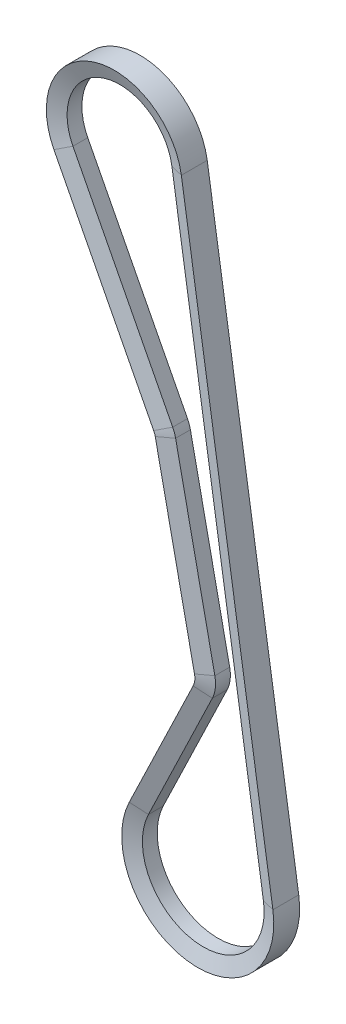
SolidWorks part; units mm, degrees
ref_plane "Front Plane" through (0, 0, 0) normal (0, 0, 1) x (1, 0, 0)
ref_plane "Top Plane" through (0, 0, 0) normal (0, 1, 0) x (1, 0, 0)
ref_plane "Right Plane" through (0, 0, 0) normal (1, 0, 0) x (0, 0, -1)
sketch "Sketch2" plane through (0, 0, 0) normal (0, 0, 1) x (1, 0, 0)
  line L0 (0, 0) -> (1, 0) construction
  line L1 (0, 0) -> (0, 1) construction
  line L12 (24.7047, 3.831) -> (58.414, -213.5505)
  line L14 (5.5201, -205.6872) -> (29.0529, -156.8468)
  line L15 (29.5453, -152.7788) -> (15.0861, -84.2884)
  line L16 (14.5167, -82.6895) -> (-22.2191, -11.4591)
  arc A4 (58.414, -213.5505) -> (5.5201, -205.6872) centre (30.7447, -217.8411) cw
  arc A7 (-22.2191, -11.4591) -> (24.7047, 3.831) centre (0, 0) cw
  arc A8 (29.0529, -156.8468) -> (29.5453, -152.7788) centre (23.3323, -154.0904) ccw
  arc A9 (15.0861, -84.2884) -> (14.5167, -82.6895) centre (8.873, -85.6001) ccw
ref_plane "Plane4" through (-22.2191, -11.4591, 0) normal (-0.4584, 0.8888, 0) x (0.8888, 0.4584, 0)
sketch "Sketch3" plane through (-22.2191, -11.4591, 0) normal (-0.4584, 0.8888, 0) x (0.8888, 0.4584, 0)
  line L0 (0, -4.7625) -> (0, 4.7625)
  line L1 (0, -4.7625) -> (5.588, -2.7286)
  line L2 (5.588, -2.7286) -> (5.588, 2.7286)
  line L3 (5.588, 2.7286) -> (0, 4.7625)
  line L4 (0, 0) -> (5.588, 0) construction
  dimension "D1" = 9.525
  dimension "D2" = 5.588
  dimension "D3" = 40
sweep "Sweep1" add profiles "Sketch3" path "Sketch2"
